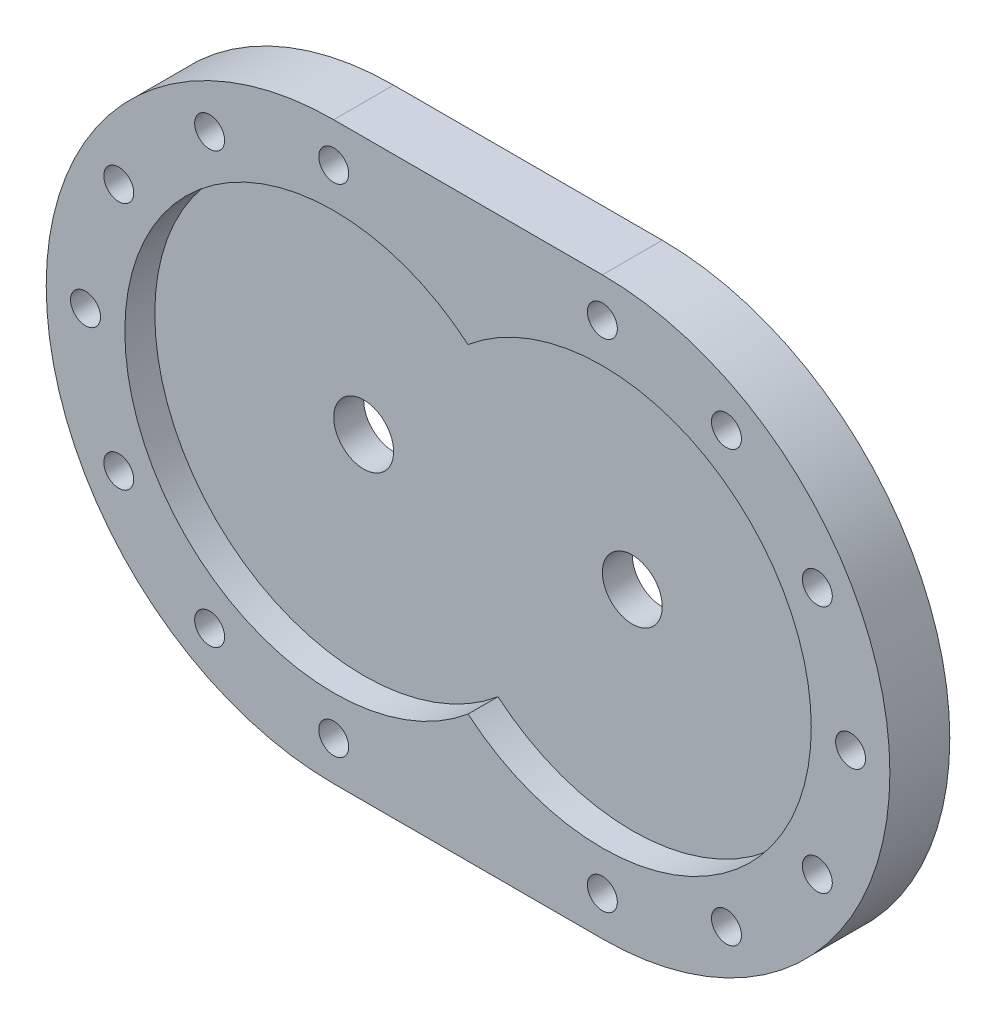
SolidWorks part; units mm, degrees
ref_plane "Ön Düzlem" through (0, 0, 0) normal (0, 0, 1) x (1, 0, 0)
ref_plane "Üst Düzlem" through (0, 0, 0) normal (0, 1, 0) x (1, 0, 0)
ref_plane "Sağ Düzlem" through (0, 0, 0) normal (1, 0, 0) x (0, 0, -1)
sketch "Çizim1" plane through (0, 0, 0) normal (0, 0, 1) x (1, 0, 0)
  line L0 (0, 66.02) -> (0, -66.02) construction
  line L1 (44.845, 0) -> (114.595, 0) construction
  line L2 (114.595, 0) -> (127.72, 0) construction
  line L3 (-44.845, 0) -> (-44.845, -96) construction
  line L4 (-44.845, -96) -> (44.845, -96)
  line L5 (-44.845, 0) -> (-44.845, 96) construction
  line L6 (-44.845, 96) -> (44.845, 96)
  circle A0 centre (-44.845, 0) radius 10
  circle A1 centre (44.845, 0) radius 10
  arc A2 (0, 84.8818) -> (0, -84.8818) centre (-44.845, 0) ccw
  arc A4 (0, 53.4227) -> (0, -53.4227) centre (-44.845, 0) ccw
  arc A5 (0, -53.4227) -> (0, 53.4227) centre (44.845, 0) ccw
  arc A6 (0, -84.8818) -> (0, 84.8818) centre (44.845, 0) ccw
  circle A7 centre (127.72, 0) radius 5
  circle A8 centre (116.6169, 41.4375) radius 5
  circle A9 centre (86.2825, 71.7719) radius 5
  circle A10 centre (44.845, 82.875) radius 5
  circle A11 centre (44.845, -82.875) radius 5
  circle A12 centre (86.2825, -71.7719) radius 5
  circle A13 centre (116.6169, -41.4375) radius 5
  circle A14 centre (-44.845, -82.875) radius 5
  circle A15 centre (-86.2825, -71.7719) radius 5
  circle A16 centre (-116.6169, -41.4375) radius 5
  circle A17 centre (-127.72, 0) radius 5
  circle A18 centre (-116.6169, 41.4375) radius 5
  circle A19 centre (-86.2825, 71.7719) radius 5
  circle A20 centre (-44.845, 82.875) radius 5
  point P4 (0, 0)
  point P24 (44.845, 0)
  dimension "D1" = 20
  dimension "D2" = 20
  dimension "D5" = 192
  dimension "D6" = 96
  dimension "D7" = 139.5
  dimension "D8" = 13.125
  dimension "D9" = 10
  dimension "D3" = 89.69
  dimension "D4" = 44.845
  dimension "D11" = 41.4375
  dimension "D12" = 71.7719
  dimension "D13" = 82.875
  dimension "D14" = 89.69
  dimension "D15" = 96
  dimension "D16" = 89.69
  dimension "D17" = 96
  dimension "D10" = 4
extrude "Yükseklik-Ekstrüzyon1" add sketch "Çizim1" along normal blind 20 contours A2 A6 A19 A17 A16 A15 A14 A12 A5 A4 A7 A8 A9 A10 A11 A13 A18 A20 region at (-137.436, 0, 0)
extrude "Yükseklik-Ekstrüzyon2" add sketch "Çizim1<3>" along normal blind 10 contours A4 A5 A0 A1 region at (0, 0, 0)
sketch "Çizim1<3>" plane through (0, 0, 0) normal (0, 0, 1) x (1, 0, 0) same geometry as "Çizim1"
extrude "Yükseklik-Ekstrüzyon3" add sketch "Çizim1<5>" along normal blind 20 contours A6 L6 A2 | A6 A2 L4 region at (0, -92.7005, 0) region at (0, 92.7005, 0)
sketch "Çizim1<5>" plane through (0, 0, 0) normal (0, 0, 1) x (1, 0, 0) same geometry as "Çizim1"
